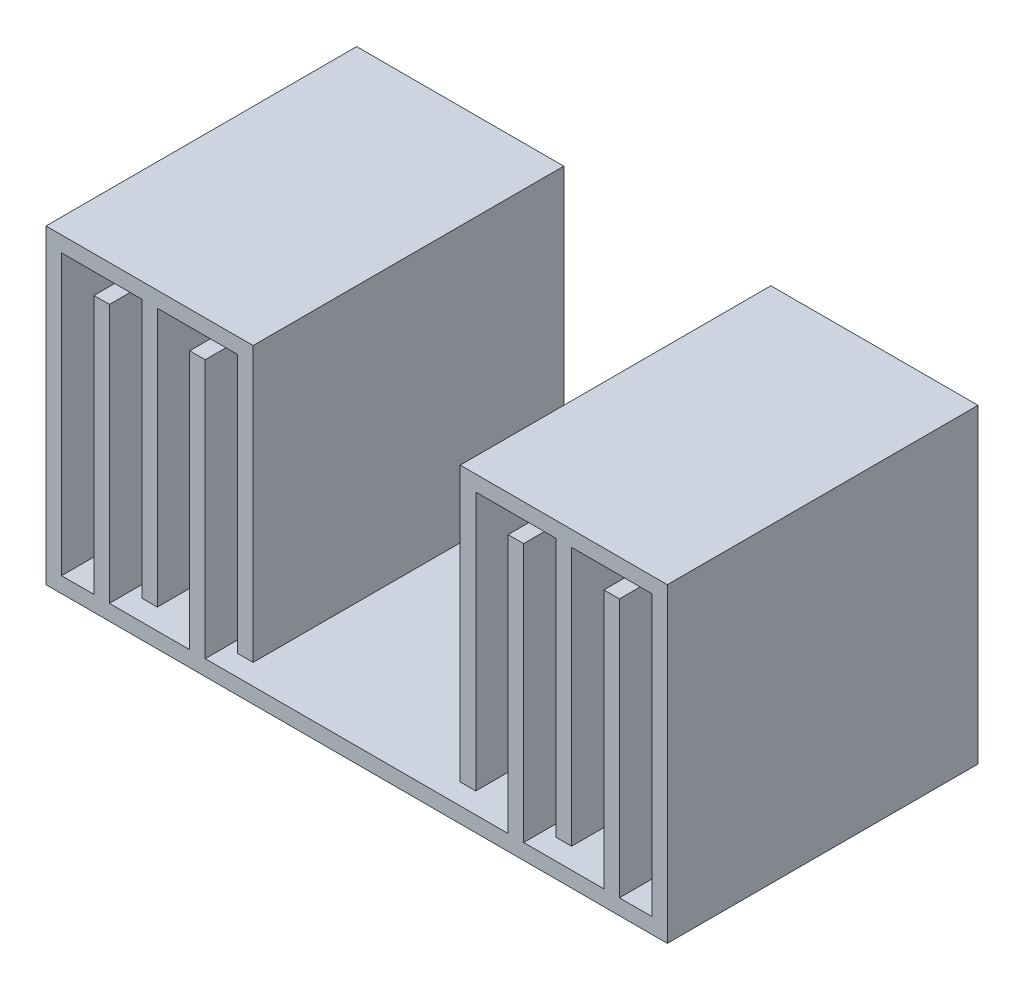
SolidWorks part; units mm, degrees
material "ABS"
ref_plane "Front Plane" through (0, 0, 0) normal (0, 0, 1) x (1, 0, 0)
ref_plane "Top Plane" through (0, 0, 0) normal (0, 1, 0) x (1, 0, 0)
ref_plane "Right Plane" through (0, 0, 0) normal (1, 0, 0) x (0, 0, -1)
sketch "Sketch1" plane through (0, 0, 0) normal (0, 0, 1) x (1, 0, 0)
  line L1 (-30, -15) -> (30, -15)
  line L2 (-30, -15) -> (-30, 15)
  line L3 (-30, 15) -> (30, 15)
  line L4 (30, -15) -> (30, 15)
  line L5 (0, 15) -> (0, -15) construction
  line L6 (-30, 0) -> (30, 0) construction
  point P16 (0, 0)
extrude "Boss-Extrude1" add sketch "Sketch1" against normal blind 30
sketch "Sketch2" plane through (0, 0, 0) normal (0, 0, 1) x (1, 0, 0)
  line L0 (30, 15) -> (-30, 15) construction
  line L1 (-10, -13.5) -> (10, -13.5)
  line L2 (-10, -13.5) -> (-10, 15)
  line L3 (-10, 15) -> (10, 15)
  line L4 (10, -13.5) -> (10, 15)
  line L5 (0, 15) -> (0, -13.5) construction
  line L6 (-10, 0.75) -> (10, 0.75) construction
  point P20 (0, 0.75)
extrude "Cut-Extrude1" cut sketch "Sketch2" against normal through all
sketch "Sketch3" plane through (0, 0, 0) normal (0, 0, 1) x (1, 0, 0)
  line L1 (-28.5, -13.5) -> (-11.5, -13.5)
  line L2 (-28.5, -13.5) -> (-28.5, 13.5)
  line L3 (-28.5, 13.5) -> (-11.5, 13.5)
  line L4 (-11.5, -13.5) -> (-11.5, 13.5)
  line L5 (-20, 13.5) -> (-20, -13.5) construction
  line L6 (-28.5, 0) -> (-11.5, 0) construction
  line L7 (11.5, -13.5) -> (28.5, -13.5)
  line L8 (11.5, -13.5) -> (11.5, 13.5)
  line L9 (11.5, 13.5) -> (28.5, 13.5)
  line L10 (28.5, -13.5) -> (28.5, 13.5)
  line L11 (20, 13.5) -> (20, -13.5) construction
  line L12 (11.5, 0) -> (28.5, 0) construction
  point P16 (-20, 0)
  point P25 (20, 0)
extrude "Cut-Extrude2" cut sketch "Sketch3" against normal blind 28.5
sketch "Sketch4" plane through (0, 0, 0) normal (0, 0, 1) x (1, 0, 0)
  line L0 (-28.5, -13.5) -> (-11.5, -13.5) construction
  line L1 (-16.125, -13.5) -> (-14.625, -13.5)
  line L2 (-16.125, -13.5) -> (-16.125, 11.5)
  line L3 (-16.125, 11.5) -> (-14.625, 11.5)
  line L4 (-14.625, -13.5) -> (-14.625, 11.5)
  line L5 (-15.375, 11.5) -> (-15.375, -13.5) construction
  line L6 (-16.125, -1) -> (-14.625, -1) construction
  line L7 (-11.5, 13.5) -> (-28.5, 13.5) construction
  line L8 (-20.75, -11.5) -> (-19.25, -11.5)
  line L9 (-20.75, -11.5) -> (-20.75, 13.5)
  line L10 (-20.75, 13.5) -> (-19.25, 13.5)
  line L11 (-19.25, -11.5) -> (-19.25, 13.5)
  line L12 (-20, 13.5) -> (-20, -11.5) construction
  line L13 (-20.75, 1) -> (-19.25, 1) construction
  line L14 (11.5, -13.5) -> (28.5, -13.5) construction
  line L15 (-25.375, -13.5) -> (-23.875, -13.5)
  line L16 (-25.375, -13.5) -> (-25.375, 11.5)
  line L17 (-25.375, 11.5) -> (-23.875, 11.5)
  line L18 (-23.875, -13.5) -> (-23.875, 11.5)
  line L19 (-24.625, 11.5) -> (-24.625, -13.5) construction
  line L20 (-25.375, -1) -> (-23.875, -1) construction
  line L21 (14.625, -13.5) -> (16.125, -13.5)
  line L22 (14.625, -13.5) -> (14.625, 11.5)
  line L23 (14.625, 11.5) -> (16.125, 11.5)
  line L24 (16.125, -13.5) -> (16.125, 11.5)
  line L25 (15.375, 11.5) -> (15.375, -13.5) construction
  line L26 (14.625, -1) -> (16.125, -1) construction
  line L27 (28.5, 13.5) -> (11.5, 13.5) construction
  line L28 (19.25, -11.5) -> (20.75, -11.5)
  line L29 (19.25, -11.5) -> (19.25, 13.5)
  line L30 (19.25, 13.5) -> (20.75, 13.5)
  line L31 (20.75, -11.5) -> (20.75, 13.5)
  line L32 (20, 13.5) -> (20, -11.5) construction
  line L33 (19.25, 1) -> (20.75, 1) construction
  line L35 (23.875, -13.5) -> (25.375, -13.5)
  line L36 (23.875, -13.5) -> (23.875, 11.5)
  line L37 (23.875, 11.5) -> (25.375, 11.5)
  line L38 (25.375, -13.5) -> (25.375, 11.5)
  line L39 (24.625, 11.5) -> (24.625, -13.5) construction
  line L40 (23.875, -1) -> (25.375, -1) construction
  point P16 (-15.375, -1)
  point P31 (-20, 1)
  point P38 (-24.625, -1)
  point P47 (15.375, -1)
  point P62 (20, 1)
  point P69 (24.625, -1)
extrude "Boss-Extrude2" add sketch "Sketch4" against normal blind 28.5
sketch "Sketch5" plane through (0, 0, 0) normal (0, 0, 1) x (1, 0, 0)
  line L0 (-10, 15) -> (-10, -13.5) construction
  line L1 (-11.5, -13.5) -> (-10, -13.5)
  line L2 (-11.5, -13.5) -> (-11.5, -11.5)
  line L3 (-11.5, -11.5) -> (-10, -11.5)
  line L4 (-10, -13.5) -> (-10, -11.5)
  line L5 (-10.75, -11.5) -> (-10.75, -13.5) construction
  line L6 (-11.5, -12.5) -> (-10, -12.5) construction
  line L7 (11.5, 13.5) -> (11.5, -13.5) construction
  line L8 (10, -13.5) -> (11.5, -13.5)
  line L9 (10, -13.5) -> (10, -11.5)
  line L10 (10, -11.5) -> (11.5, -11.5)
  line L11 (11.5, -13.5) -> (11.5, -11.5)
  line L12 (10.75, -11.5) -> (10.75, -13.5) construction
  line L13 (10, -12.5) -> (11.5, -12.5) construction
  point P20 (-10.75, -12.5)
  point P32 (10.75, -12.5)
extrude "Cut-Extrude3" cut sketch "Sketch5" against normal blind 28.5
equation "\"W_cell\" = 60mm"
equation "\"H_cell\" = 30mm"
equation "\"D_cell\" = 30mm"
equation "\"W_airway\" = 20mm"
equation "\"t_wall\" = 1.5mm"
equation "\"w_slit_entry\" = 2.0mm"
equation "\"N_passes\" = 4"
equation "\"W_chamber\" = (\"W_cell\" - \"W_airway\") / 2"
equation "\"w_slit\" = (\"W_chamber\" - (\"N_passes\" + 1) * \"t_wall\") / \"N_passes\""
equation "\"L_baffle\" = \"H_cell\" - (2 * \"t_wall\") - \"w_slit_entry\""
equation "\"L_waveguide\" = 100mm"
